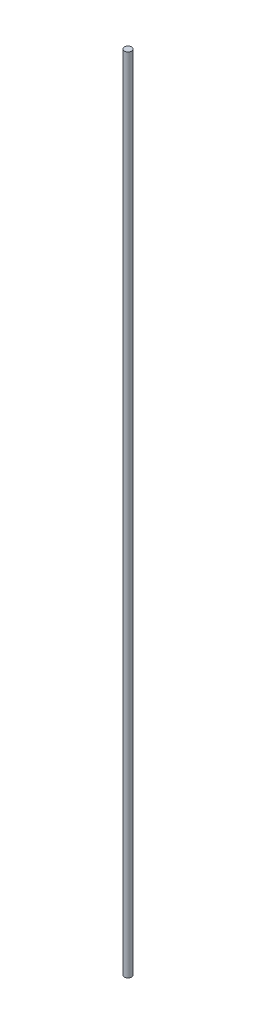
SolidWorks part; units mm, degrees
ref_plane "Спереди" through (0, 0, 0) normal (0, 0, 1) x (1, 0, 0)
ref_plane "Сверху" through (0, 0, 0) normal (0, 1, 0) x (1, 0, 0)
ref_plane "Справа" through (0, 0, 0) normal (1, 0, 0) x (0, 0, -1)
sketch "Эскиз2" plane through (0, 0, 0) normal (0, 0, 1) x (1, 0, 0)
  line L5 (-2.5, 275) -> (0, 275)
  line L6 (-2.5, 275) -> (-2.5, -275)
  line L7 (-2.5, -275) -> (0, -275)
  line L8 (0, 275) -> (0, -275)
  line L9 (-2.5, 275) -> (0, -275) construction
  line L10 (-2.5, -275) -> (0, 275) construction
  point P0 (-1.25, 0)
  point P5 (0, 0)
  dimension "D1" = 2.5
  dimension "D2" = 550
revolve "Повернуть1" add sketch "Эскиз2" angle 360 about L6
equation "\"Ширина груза\"= 420"
equation "\"Глубина груза\"= 490"
equation "\"Высота груза\"= 297"
equation "\"Ширина ячейки\"= \"Ширина груза\" + 10"
equation "\"Глубина ячейки\"= \"Глубина груза\" + 10"
equation "\"Высота ячейки\"= \"Высота груза\" + 10 + 13"
equation "\"Колво ячеек ширина\"= 2"
equation "\"Колво ячеек высота\"= 2"
equation "\"Толщина стенки\" = 6"
equation "\"Крепление дверцы\"= 5 "
equation "\"Ширина рейки\"= \"Толщина шестерни\""
equation "\"Высота рейки\"= 20"
equation "\"Высота пола\"= \"Толщина стенки\" * 2"
equation "\"Колво полозьев\"= 5"
equation "\"Отступ рейки\"= 20"
equation "\"Глубина каретки\"= \"Глубина ячейки\" + 30 + \"Мотор Y высота корпуса\" + 20"
equation "\"Длинна рейки\"= ( \"Ширина ячейки\" + \"Толщина стенки\" + \"Крепление дверцы\" ) * \"Колво ячеек ширина\" + \"Ширина ячейки выгрузки\" * \"Колво выгрузки\" + \"Толщина стенки\""
equation "\"Отступ шпильки\"= 26"
equation "\"Диаметр шпильки\"= 5"
equation "\"Длинна шпильки\"= ( \"Высота ячейки\" + \"Толщина стенки\" + \"Высота пола\" ) * \"Колво ячеек высота\" + ( \"Толщина стенки\" + \"Отступ рейки\" ) * 2 "
equation "\"D1@Эскиз2\"= \"Диаметр шпильки\" / 2"
equation "\"D2@Эскиз2\"= \"Глубина каретки\" - \"Мотор Y высота корпуса\""
equation "\"Ширина пластины\"= 50  "
equation "\"Высота зона выгрузки\"= \"Высота ячейки\" * 2 + \"Толщина стенки\" * 2"
equation "\"Колво выгрузки\"= 1"
equation "\"Отступ крепления мотора фиксации\" = 30"
equation "\"Мотор X ширина корпуса\"= 42.3"
equation "\"Мотор X высота корпуса\"= 42.3"
equation "\"Мотор X длина корпуса\"= 40"
equation "\"Мотор X вылет вала\"= 19.8"
equation "\"Мотор Y ширина корпуса\"= 42.3"
equation "\"Мотор Y высота корпуса\"= 42.3"
equation "\"Мотор Y длина корпуса\"= 48"
equation "\"Мотор Y вылет вала\"= 30"
equation "\"Мотор Z ширина корпуса\"= 42"
equation "\"Мотор Z высота корпуса\"= 42"
equation "\"Мотор Z длина корпуса\"= 40"
equation "\"Мотор Z вылет вала\"= 23"
equation "\"Мотор диаметр вала ПРЕДВ\"= 5"
equation "\"Мотор шаг крепления ПРЕДВ\"= 31"
equation "\"Мотор диаметр отверстий ПРЕДВ\"= 3"
equation "\"Мотор глубина отверстий ПРЕДВ\"= 4.5"
equation "\"Мотор диаметр буртика ПРЕДВ\"= 22"
equation "\"Мотор высота буртика ПРЕДВ\"= 2"
equation "\"Мотор диаметр шкива ПРЕДВ\"= 16"
equation "\"Мотор длина шкива ПРЕДВ\"= 12"
equation "\"Мотор отступ шкива ПРЕДВ\"= 5"
equation "\"Мотор X шаг градусов\"= 1.8"
equation "\"Мотор X ток А\"= 1.5"
equation "\"Мотор X сопротивление Ом\"= 1.3"
equation "\"Мотор X индуктивность мГн\"= 2"
equation "\"Мотор Y шаг градусов\"= 1.8"
equation "\"Мотор Y ток А\"= 2.2"
equation "\"Мотор Y сопротивление Ом\"= 0.9"
equation "\"Мотор Y индуктивность мГн\"= 2"
equation "\"Мотор Z шаг градусов\"= 1.8"
equation "\"Мотор Z ток А\"= 1"
equation "\"Мотор Z сопротивление Ом\"= 4"
equation "\"Мотор Z индуктивность мГн\"= 8"
equation "\"Мотор Y диаметр ротора\"= 25.78"
equation "\"Ширина ячейки выгрузки\"= \"Ширина ячейки\" + \"Толщина стенки\" + \"Отступ крепления мотора фиксации\"*2"
